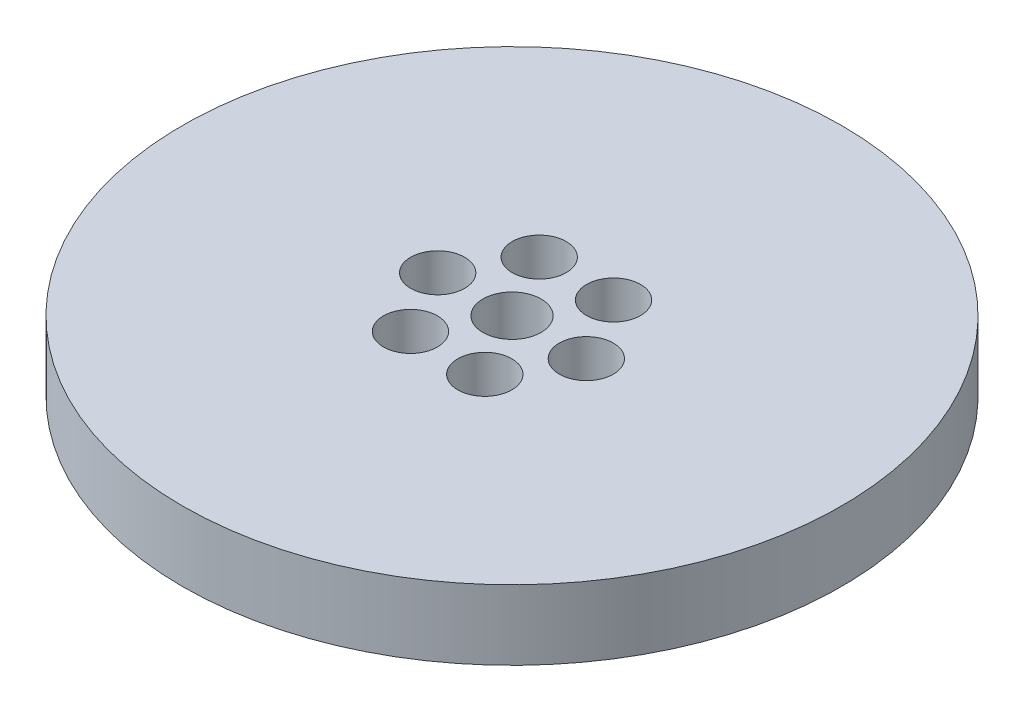
SolidWorks part; units mm, degrees
ref_plane "Front Plane" through (0, 0, 0) normal (0, 0, 1) x (1, 0, 0)
ref_plane "Top Plane" through (0, 0, 0) normal (0, 1, 0) x (1, 0, 0)
ref_plane "Right Plane" through (0, 0, 0) normal (1, 0, 0) x (0, 0, -1)
sketch "Sketch1" plane through (0, 0, 0) normal (0, 1, 0) x (1, 0, 0)
  circle A0 centre (0, 0) radius 85
  dimension "FLANGE_OD" = 170
extrude "Boss-Extrude1" add sketch "Sketch1" along normal blind 18
sketch "Sketch2" plane through (0, 0, 0) normal (0, 1, 0) x (1, 0, 0)
  circle A0 centre (0, 0) radius 7.5
  dimension "BORE_D" = 15
extrude "Cut-Extrude1" cut sketch "Sketch2" along normal through all
sketch "Sketch3" plane through (0, 18, 0) normal (0, 1, 0) x (1, 0, 0)
  circle A0 centre (0, 0) radius 19.1706 construction
  circle A1 centre (-19.1706, 0) radius 6.966
  dimension "BOLT_D" = 13.9319
  dimension "BOLT_PCD" = 38.3412
extrude "Cut-Extrude2" cut sketch "Sketch3" against normal blind 11.0943
pattern_circular "CirPattern1" count 6 over 360 about axis through (0, 0, 0) along (0, 1, 0) of "Cut-Extrude2"
